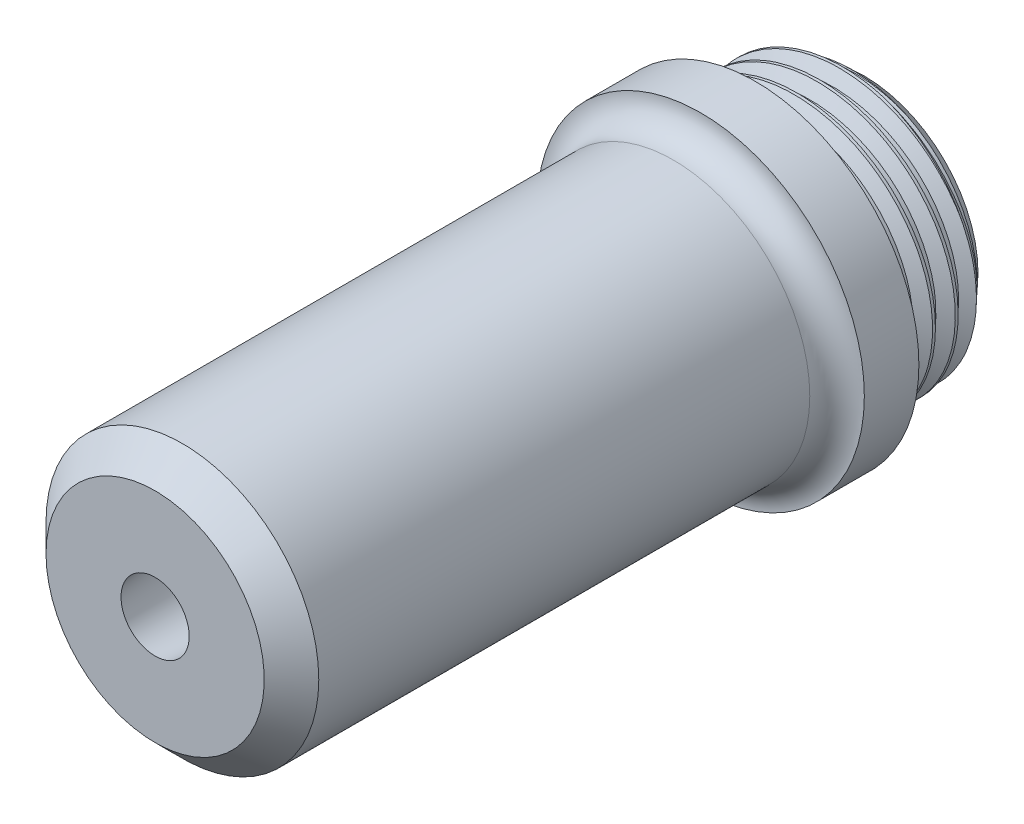
SolidWorks part; units mm, degrees
material "Plain Carbon Steel"
ref_plane "Front Plane" through (0, 0, 0) normal (0, 0, 1) x (1, 0, 0)
ref_plane "Top Plane" through (0, 0, 0) normal (0, 1, 0) x (1, 0, 0)
ref_plane "Right Plane" through (0, 0, 0) normal (1, 0, 0) x (0, 0, -1)
sketch "Sketch1" plane through (0, 0, 0) normal (0, 0, 1) x (1, 0, 0)
  circle A0 centre (0, 0) radius 7.62
  dimension "D1" = 15.24
extrude "Boss-Extrude1" add sketch "Sketch1" along normal blind 2.54
sketch "Sketch2" plane through (0, 0, 0) normal (0, 0, -1) x (-1, 0, 0)
  circle A0 centre (0, 0) radius 6.35
  dimension "D1" = 12.7
extrude "Boss-Extrude2" add sketch "Sketch2" along normal blind 5.08 and the other way blind 27.94
thread "Thread1" pitch 1.0583 method cut profile "Thread Profile1" start angle 0, offset 0, length 5.461, pitch 1.0583, diameter 12.7
ref_plane "Plane1" through (6.35, 0, -5.08) normal (0, -1, 0) x (1, 0, 0)
sketch "Thread Profile1" plane through (6.35, 0, -5.08) normal (0, -1, 0) x (1, 0, 0)
  line L0 (0, 0) -> (0, 1.0583) construction
  line L11 (0, 0) -> (0, 0.926)
  line L12 (0, 0.926) -> (-0.5728, 0.5953)
  line L13 (-0.5728, 0.5953) -> (-0.5728, 0.3307)
  line L15 (-0.5728, 0.3307) -> (0, 0)
  line L17 (-0.5728, 0.463) -> (0, 0.463) construction
  point P2 (0, 0)
  dimension "Pitch" = 1.0583
  dimension "Profile_Angle" = 60
  dimension "Profile_Land" = 0.2646
  dimension "Profile_Height" = 0.5728
sketch "Sketch6" plane through (0, 0, 0) normal (0, 1, 0) x (1, 0, 0)
  line L0 (0, 0) -> (0, 5.08) construction
  line L1 (6.35, 5.08) -> (-6.35, 5.08) construction
  line L2 (4.699, 5.715) -> (6.477, 3.81)
  line L3 (6.477, 3.81) -> (6.477, 5.715)
  line L4 (6.477, 5.715) -> (4.699, 5.715)
  dimension "D1" = 4.699
  dimension "D2" = 1.778
  dimension "D3" = 1.905
  dimension "D4" = 0.635
revolve "Cut-Revolve1" cut sketch "Sketch6" angle 360 about L0
fillet "Fillet1" radius 1.27 1 edges at (6.35, 0, 2.54)
chamfer "Chamfer1" distance 1.27 angle 45 1 edges at (-6.35, 0, 27.94)
sketch "Sketch7" plane through (0, 0, 27.94) normal (0, 0, 1) x (1, 0, 0)
  circle A0 centre (0, 0) radius 1.5875
  dimension "D1" = 3.175
extrude "Cut-Extrude1" cut sketch "Sketch7" against normal through all draft 5 draft outward yes
